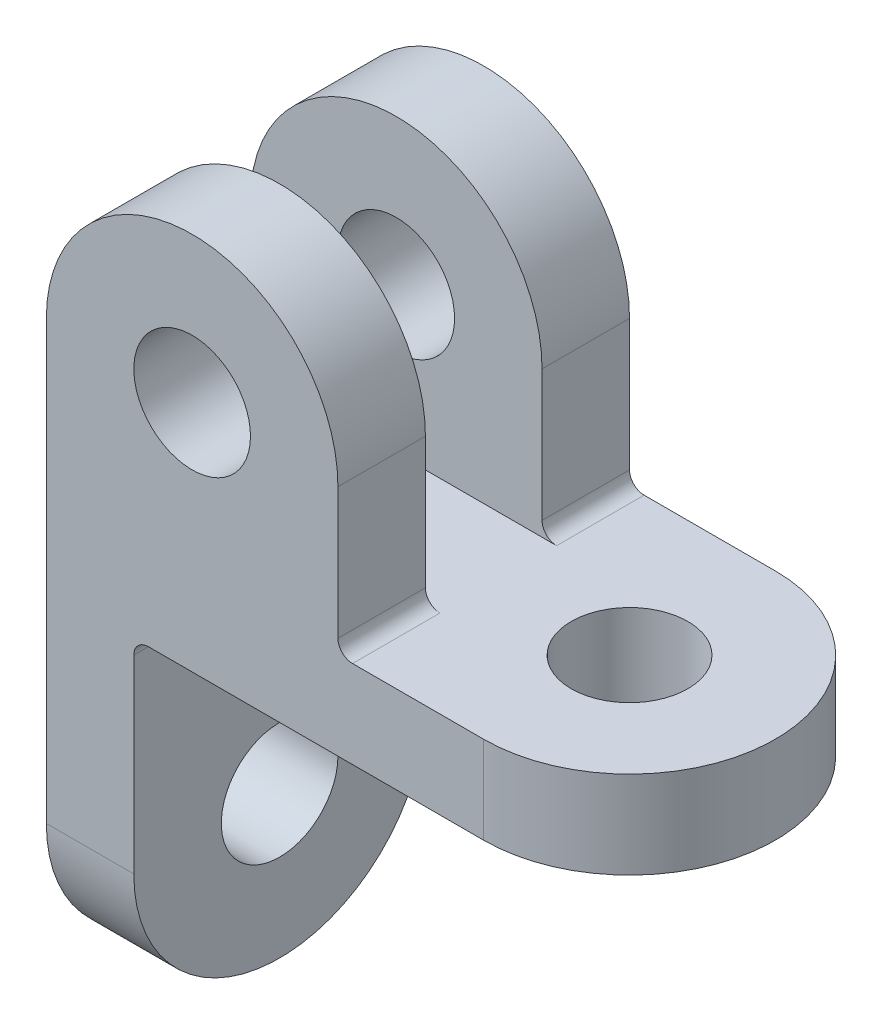
SolidWorks part; units mm, degrees
ref_plane "Front Plane" through (0, 0, 0) normal (0, 0, 1) x (1, 0, 0)
ref_plane "Top Plane" through (0, 0, 0) normal (0, 1, 0) x (1, 0, 0)
ref_plane "Right Plane" through (0, 0, 0) normal (1, 0, 0) x (0, 0, -1)
sketch "Sketch1" plane through (0, 0, 0) normal (0, 0, 1) x (1, 0, 0)
  line L2 (0, 60) -> (0, 0)
  line L3 (30, 60) -> (30, 45)
  line L4 (30, 45) -> (60, 45)
  line L5 (60, 45) -> (60, 36)
  line L6 (60, 36) -> (9, 36)
  line L7 (9, 36) -> (9, 0)
  line L8 (9, 0) -> (0, 0)
  line L9 (30, 45) -> (0, 45)
  arc A0 (0, 60) -> (30, 60) centre (15, 60) cw
  circle A1 centre (15, 60) radius 6
  dimension "D2" = 15
  dimension "D6" = 12
  dimension "D1" = 60
  dimension "D3" = 15
  dimension "D4" = 30
  dimension "D5" = 9
  dimension "D7" = 9
extrude "Boss-Extrude1" add sketch "Sketch1" along normal mid plane 30 contours L4 L9 L2 L8 L7 L6 L5 region at (15, 44.25, 0)
extrude "Boss-Extrude2" add sketch "Sketch1<5>" along normal blind 9 from offset 6 contours A0 L2 L9 L3 A1 region at (15, 74.5757, 0)
sketch "Sketch1<5>" plane through (0, 0, 0) normal (0, 0, 1) x (1, 0, 0) same geometry as "Sketch1"
extrude "Boss-Extrude5" add sketch "Sketch1<8>" against normal blind 9 from offset 6 contours A0 L2 L9 L3 A1 region at (15, 74.5757, 0) offset against normal yes
sketch "Sketch1<8>" plane through (0, 0, 0) normal (0, 0, 1) x (1, 0, 0) same geometry as "Sketch1"
fillet "Fillet1" 2 edges at (60, 40.5, 15) (60, 40.5, -15) type full round first side face at (24.75, 37.125, 15) second side face at (24.75, 37.125, -15) middle face at (60, 40.5, 0)
fillet "Fillet2" 2 edges at (4.5, 0, 15) (4.5, 0, -15) type full round first side face at (21, 37.125, 15) second side face at (21, 37.125, -15) middle face at (4.5, 0, 0)
hole_wizard "Ø12.0mm Dowel Hole1" positions "3DSketch1" profile "Sketch2" hole size "Ø12.0" standard "ISO" end condition up to next
sketch3d "3DSketch1"
  line L0 (45, 45, 0) -> (45, 36, 0) construction
  line L1 (9, 15, 0) -> (0, 15, 0) construction
  point P0 (45, 45, 0)
  point P4 (9, 15, 0)
sketch "Sketch2" plane through (45, 45, 0) normal (1, 0, 0) x (0, 0, 1)
  line L0 (0, 0) -> (0, 9)
  line L1 (0, 9) -> (6, 9)
  line L2 (6, 9) -> (6, 0)
  line L5 (6, 0) -> (0, 0)
  line L11 (0, -6.35) -> (0, 107.95) construction
  dimension "Thru Hole Dia." = 12
  dimension "Thru Hole Depth" = 9
fillet "Fillet3" radius 1.5 3 edges at (30, 45, -10.5) (30, 45, 10.5) (9, 36, 0)
